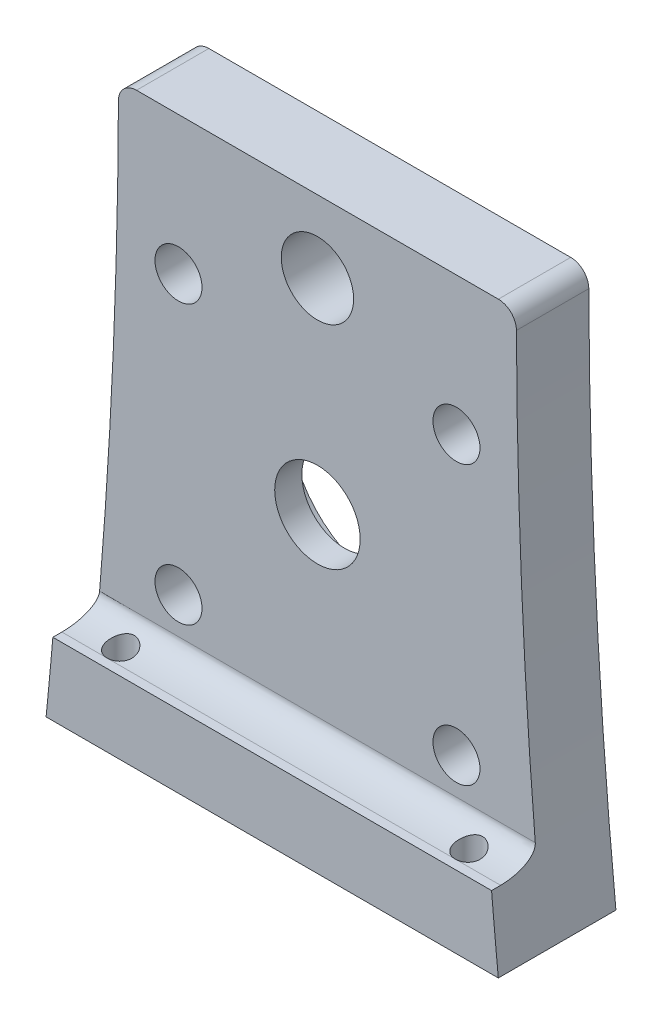
SolidWorks part; units mm, degrees
ref_plane "Front Plane" through (0, 0, 0) normal (0, 0, 1) x (1, 0, 0)
ref_plane "Top Plane" through (0, 0, 0) normal (0, 1, 0) x (1, 0, 0)
ref_plane "Right Plane" through (0, 0, 0) normal (1, 0, 0) x (0, 0, -1)
sketch "Sketch1" plane through (0, 0, 0) normal (0, 0, 1) x (1, 0, 0)
  line L0 (-22, 60) -> (-22, 0) construction
  line L3 (22, 60) -> (-22, 60)
  line L5 (25, 0) -> (-25, 0)
  line L6 (0, 60) -> (0, 0) construction
  arc A0 (-25, 0) -> (-22, 60) centre (-623.5, 60) ccw
  arc A1 (25, 0) -> (22, 60) centre (623.5, 60) cw
  dimension "D1" = 60
  dimension "D2" = 25
  dimension "D3" = 22
extrude "Boss-Extrude1" add sketch "Sketch1" along normal blind 8
sketch "Sketch2" plane through (0, 0, 8) normal (0, 0, 1) x (1, 0, 0)
  line L0 (-25, 0) -> (25, 0) construction
  line L1 (-25, 0) -> (25, 0)
  line L2 (-24.2519, 8) -> (24.2519, 8)
  arc A0 (22, 60) -> (25, 0) centre (623.5, 60) ccw construction
  arc A1 (-25, 0) -> (-22, 60) centre (-623.5, 60) ccw construction
  arc A2 (24.2519, 8) -> (25, 0) centre (623.5, 60) ccw
  arc A3 (-25, 0) -> (-24.2519, 8) centre (-623.5, 60) ccw
  dimension "D1" = 8
extrude "Boss-Extrude2" add sketch "Sketch2" along normal blind 5
sketch "Sketch3" plane through (0, 8, 0) normal (0, 1, 0) x (1, 0, 0)
  line L0 (-24.2519, -10.5) -> (24.2519, -10.5) construction
  line L1 (-24.2519, -13) -> (-24.2519, -8) construction
  line L2 (24.2519, -13) -> (24.2519, -8) construction
  line L3 (0, 0) -> (0, -13) construction
  line L4 (24.2519, -13) -> (-24.2519, -13) construction
  circle A0 centre (-19.2519, -10.5) radius 1.5
  circle A1 centre (19.2519, -10.5) radius 1.5
  dimension "D1" = 3
  dimension "D2" = 5
extrude "Cut-Extrude" cut sketch "Sketch3" against normal up to surface (8 mm away) up to face at (0, 0, 6.5)
fillet "Fillet1" radius 2 1 edges at (0, 8, 8) second distance 4 first distance on face at (0, 33.9878, 8)
fillet "Fillet2" radius 2 2 edges at (22, 60, 4) (-22, 60, 4)
sketch "Sketch4" plane through (0, 0, 0) normal (0, 0, -1) x (-1, 0, 0)
  line L0 (-20.0033, 60) -> (20.0033, 60) construction
  line L1 (-4.725, 29.37) -> (4.725, 29.37) construction
  line L2 (0, 34.095) -> (0, 7.695) construction
  line L3 (0, 34.095) -> (0, 24.645) construction
  circle A0 centre (0, 52) radius 4.0005
  circle A1 centre (0, 29.37) radius 4.725
  dimension "D1" = 8.001
  dimension "D3" = 9.45
  dimension "D2" = 8
  dimension "D4" = 22.63
extrude "M4*H6 T-Insert" cut sketch "Sketch4" against normal up to surface (8 mm away) up to face at (-3.6672, 42.8066, 8)
sketch "Sketch7" [suppressed] plane through (0, 0, 7) normal (0, 0, 1) x (1, 0, 0)
  line L0 (-13.3326, 40) -> (13.3326, 40)
  line L2 (11.0033, 60) -> (-11.0033, 60)
  line L3 (-15.0817, 10) -> (15.0817, 10)
  line L4 (11.0033, 60) -> (-11.0033, 60)
  arc A0 (-15.0817, 10) -> (-13.0033, 58.0066) centre (-614.5, 60) ccw construction
  arc A1 (13.0033, 58.0066) -> (15.0817, 10) centre (614.5, 60) ccw construction
  arc A4 (13.0033, 58.0066) -> (15.0817, 10) centre (614.5, 60) ccw
  arc A5 (13.0033, 58.0066) -> (11.0033, 60) centre (11.0033, 58) ccw
  arc A6 (-11.0033, 60) -> (-13.0033, 58.0066) centre (-11.0033, 58) ccw
  arc A7 (-15.0817, 10) -> (-13.0033, 58.0066) centre (-614.5, 60) ccw
  arc A8 (13.0033, 58.0066) -> (13.3326, 40) centre (614.5, 60) ccw
  arc A9 (13.0033, 58.0066) -> (11.0033, 60) centre (11.0033, 58) ccw
  arc A10 (-11.0033, 60) -> (-13.0033, 58.0066) centre (-11.0033, 58) ccw
  arc A11 (-13.3326, 40) -> (-13.0033, 58.0066) centre (-614.5, 60) ccw
  dimension "D2" = 20
  dimension "D1" = 0
sketch "Sketch8" plane through (0, 0, 0) normal (0, 0, -1) x (-1, 0, 0)
  line L0 (-20.0033, 60) -> (20.0033, 60) construction
  line L1 (23.539, 17) -> (-23.539, 17)
  line L2 (23.539, 17) -> (23.539, 57)
  line L3 (23.539, 57) -> (-23.539, 57)
  line L4 (-23.539, 17) -> (-23.539, 57)
  line L5 (25, 0) -> (-25, 0) construction
  arc A0 (22.0033, 58.0066) -> (25, 0) centre (623.5, 60) ccw construction
  arc A1 (-25, 0) -> (-22.0033, 58.0066) centre (-623.5, 60) ccw construction
  dimension "D1" = 3
  dimension "D2" = 17
extrude "Short Cut 1" [suppressed] cut sketch "Sketch8" against normal blind 10 flip side to cut
sketch "Sketch9" [suppressed] plane through (0, 0, 0) normal (1, 0, 0) x (0, 0, -1)
  line L0 (-8, 57) -> (0, 57) construction
  line L1 (0, 17) -> (-5.5, 17)
  line L2 (0, 17) -> (0, 57)
  line L3 (0, 57) -> (-5.5, 57)
  line L4 (-5.5, 17) -> (-5.5, 57)
  dimension "D1" = 5.5
extrude "Short Cut 2" [suppressed] cut sketch "Sketch9" against normal through all both and the other way through all
sketch "Sketch10" plane through (0, 0, 0) normal (0, 0, -1) x (-1, 0, 0)
  line L1 (25, 2) -> (-25, 2)
  line L2 (25, 2) -> (25, 62)
  line L3 (25, 62) -> (-25, 62)
  line L4 (-25, 2) -> (-25, 62)
  point P6 (0, 2)
  dimension "D1" = 2
  dimension "D2" = 50
  dimension "D3" = 60
extrude "Short Cut 3" [suppressed] cut sketch "Sketch10" against normal through all
sketch "Sketch12" [suppressed] plane through (0, 0, 0) normal (0, 0, -1) x (-1, 0, 0)
  line L0 (0, 40.22) -> (0, 35.22) construction
  line L1 (6, 12.22) -> (-6, 12.22)
  line L2 (6, 12.22) -> (6, 35.22)
  line L3 (6, 35.22) -> (-6, 35.22)
  line L4 (-6, 12.22) -> (-6, 35.22)
  line L5 (6, 8.22) -> (-6, 8.22) construction
  line L6 (6, 8.22) -> (6, 40.22) construction
  line L7 (6, 40.22) -> (-6, 40.22) construction
  line L8 (-6, 8.22) -> (-6, 40.22) construction
  line L9 (6, 24.22) -> (-6, 24.22) construction
  circle A0 centre (0, 29.37) radius 5.85 construction
  circle A1 centre (0, 37.72) radius 1
  circle A2 centre (0, 8.72) radius 1
  point P4 (0, 12.22)
  dimension "D3" = 11.7
  dimension "D6" = 2
  dimension "D8" = 2
  dimension "D1" = 23
  dimension "D2" = 12
  dimension "D4" = 32
  dimension "D5" = 5
  dimension "D7" = 3.5
extrude "Cut-Extrude1" [suppressed] cut sketch "Sketch12" against normal through all
sketch "Sketch13" plane through (0, 0, 0) normal (0, 0, -1) x (-1, 0, 0)
  circle A0 centre (0, 29.37) radius 11.176
  dimension "D1" = 22.352
extrude "Cut-Extrude2" cut sketch "Sketch13" against normal blind 5
sketch "Sketch14" plane through (0, 0, 0) normal (0, 0, -1) x (-1, 0, 0)
  circle A0 centre (15.364, 14.003) radius 2.6
  circle A1 centre (15.364, 44.737) radius 2.6
  circle A2 centre (-15.37, 44.737) radius 2.6
  circle A3 centre (-15.37, 14.003) radius 2.6
  circle A4 centre (0, 29.37) radius 4.725 construction
  point P8 (0, 0)
  point P9 (0, 0)
  point P10 (0, 0)
  point P11 (0, 0)
  point P12 (0, 0)
  point P13 (0, 0)
  point P14 (0, 0)
  point P15 (-64.0989, 55.7187)
  dimension "D1" = 5.2
  dimension "D2" = 5.2
  dimension "D3" = 5.2
  dimension "D4" = 5.2
  dimension "D5" = 30.734
  dimension "D6" = 15.367
  dimension "D7" = 15.37
  dimension "D8" = 30.734
extrude "Cut-Extrude3" cut sketch "Sketch14" against normal through all
